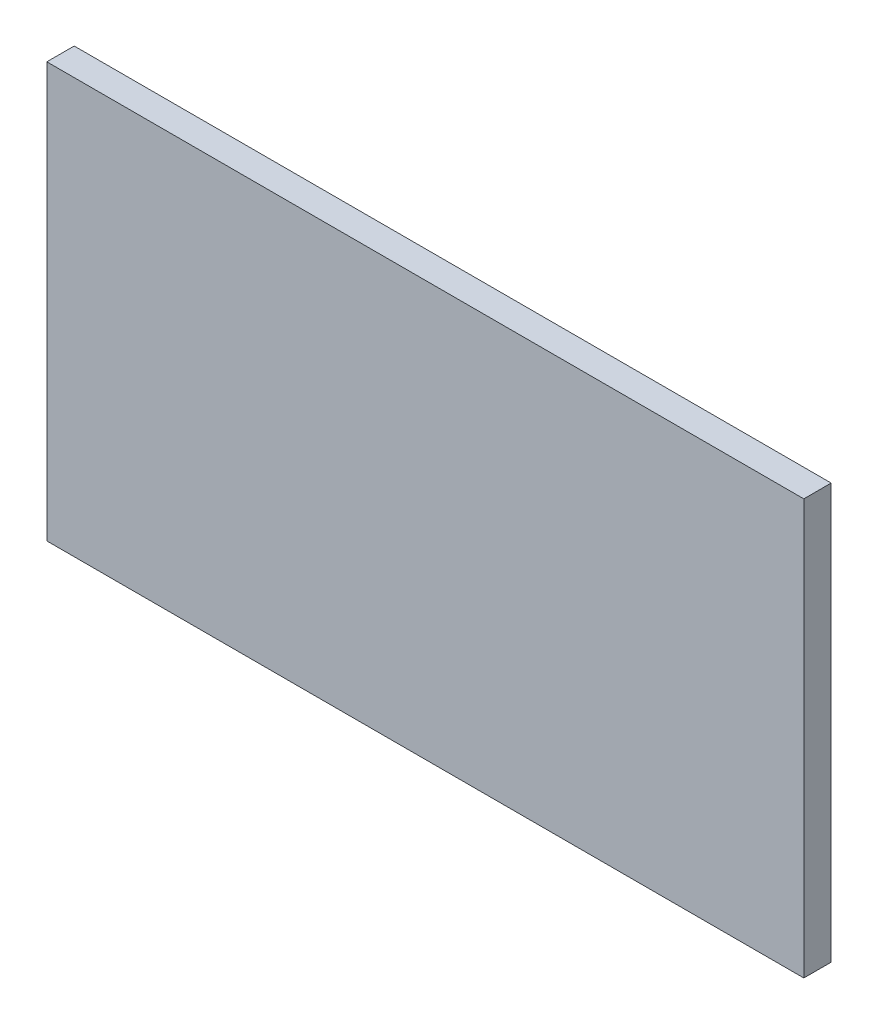
SolidWorks part; units mm, degrees
ref_plane "Front" through (0, 0, 0) normal (0, 0, 1) x (1, 0, 0)
ref_plane "Top" through (0, 0, 0) normal (0, 1, 0) x (1, 0, 0)
ref_plane "Right" through (0, 0, 0) normal (1, 0, 0) x (0, 0, -1)
sketch "Sketch1" plane through (0, 0, 0) normal (0, 0, 1) x (1, 0, 0)
  line L1 (0, 0) -> (41.5, 0)
  line L2 (0, 0) -> (0, 22.75)
  line L3 (0, 22.75) -> (41.5, 22.75)
  line L4 (41.5, 0) -> (41.5, 22.75)
  dimension "D1" = 22.75
  dimension "D2" = 41.5
extrude "Boss-Extrude1" add sketch "Sketch1" along normal blind 1.5 contours L3 L4 L1 L2
sketch "Sketch2" plane through (0, 0, 0) normal (0, 0, -1) x (-1, 0, 0)
  line L1 (-5.5, 12.25) -> (-9.26, 12.25)
  line L2 (-5.5, 12.25) -> (-5.5, 15.25)
  line L3 (-5.5, 15.25) -> (-9.26, 15.25)
  line L4 (-9.26, 12.25) -> (-9.26, 15.25)
  line L5 (0, 0) -> (0, 22.75) construction
  line L6 (0, 22.75) -> (-41.5, 22.75) construction
  dimension "D1" = 5.5
  dimension "3.7" = 3.76
  dimension "D3" = 3
  dimension "D4" = 7.5
extrude "Boss-Extrude3" add sketch "Sketch2" along normal blind 1.1
sketch "Sketch3" plane through (0, 0, -1.1) normal (0, 0, -1) x (-1, 0, 0)
  line L0 (-9.26, 13.75) -> (-5.5, 13.75) construction
  line L1 (-9.26, 15.25) -> (-9.26, 12.25) construction
  line L2 (-5.5, 12.25) -> (-5.5, 15.25) construction
  line L3 (-9.26, 12.25) -> (-5.5, 12.25) construction
  circle A0 centre (-8.08, 13.75) radius 0.25
  dimension "D1" = 1.5
  dimension "D3" = 0.5
  dimension "D2" = 1.18
extrude "Cut-Extrude1" cut sketch "Sketch3" against normal blind 0.5 contours A0
fillet "Fillet3" radius 0.5 4 edges at (9.26, 13.75, -1.1) (7.38, 15.25, -1.1) (5.5, 13.75, -1.1) (7.38, 12.25, -1.1)
sketch "Sketch4" plane through (0, 0, 0) normal (0, 0, -1) x (-1, 0, 0)
  line L0 (-41.5, 0) -> (-41.5, 22.75) construction
  line L8 (0, 0) -> (-41.5, 0) construction
  circle A0 centre (-23.25, 3.3) radius 0.65
  circle A1 centre (-23.25, 5.05) radius 0.65
  circle A2 centre (-23.25, 6.8) radius 0.65
  circle A3 centre (-21.5, 3.3) radius 0.65
  circle A4 centre (-21.5, 5.05) radius 0.65
  circle A5 centre (-21.5, 6.8) radius 0.65
  dimension "D4" = 2
  dimension "D3" = 1.3
  dimension "D1" = 3.3
  dimension "D2" = 20
  dimension "D5" = 3
extrude "Boss-Extrude6" add sketch "Sketch4" along normal blind 0.25 separate body contours A3 | A0 | A1 | A4 | A5 | A2 region at (23.25, 3.3, 0) region at (23.25, 5.05, 0) region at (23.25, 6.8, 0) region at (21.5, 3.3, 0) region at (21.5, 5.05, 0) region at (21.5, 6.8, 0)
